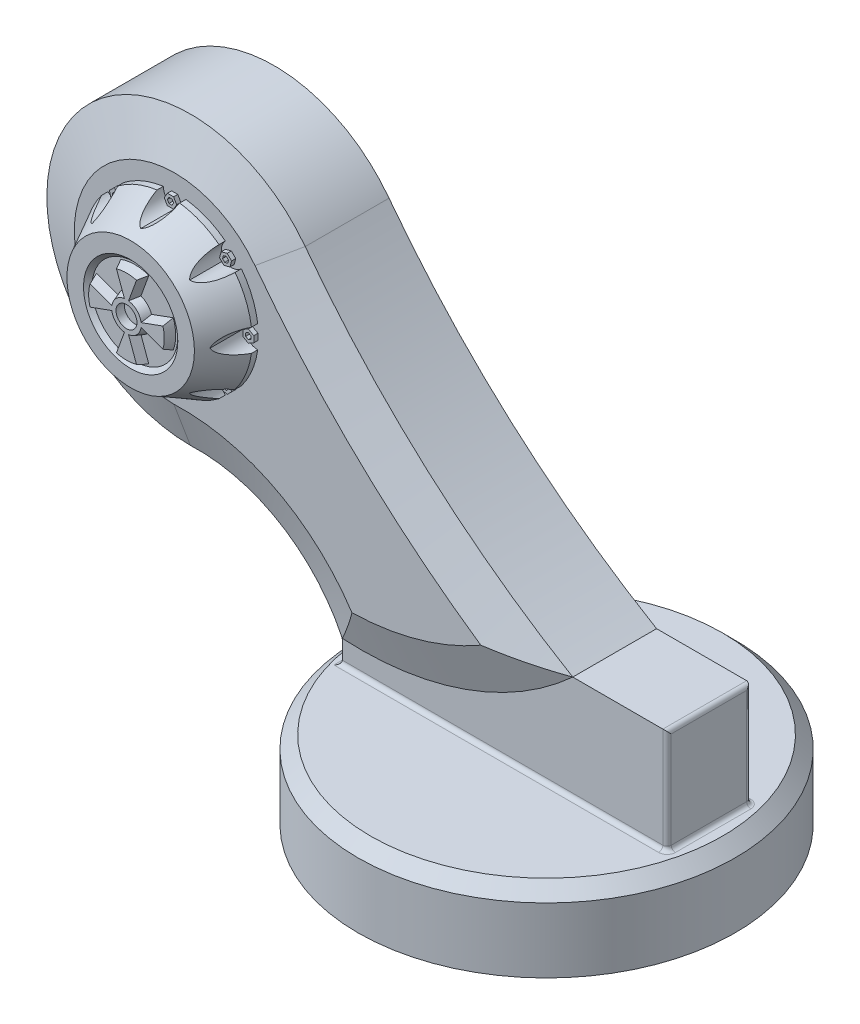
SolidWorks part; units mm, degrees
ref_plane "Front Plane" through (0, 0, 0) normal (0, 0, 1) x (1, 0, 0)
ref_plane "Top Plane" through (0, 0, 0) normal (0, 1, 0) x (1, 0, 0)
ref_plane "Right Plane" through (0, 0, 0) normal (1, 0, 0) x (0, 0, -1)
sketch "Sketch1" plane through (0, 0, 0) normal (0, 1, 0) x (1, 0, 0)
  circle A0 centre (0, 0) radius 90
  dimension "D1" = 180
extrude "Boss-Extrude1" add sketch "Sketch1" along normal blind 37
chamfer "Chamfer1" distance 6 angle 45 1 edges at (0, 37, 90)
sketch "Sketch2" plane through (0, 37, 0) normal (0, 1, 0) x (1, 0, 0)
  line L1 (-77.5, 20) -> (77.5, 20)
  line L2 (-77.5, 20) -> (-77.5, -20)
  line L3 (-77.5, -20) -> (77.5, -20)
  line L4 (77.5, 20) -> (77.5, -20)
  line L5 (-77.5, 20) -> (77.5, -20) construction
  line L6 (-77.5, -20) -> (77.5, 20) construction
  point P0 (0, 0)
  dimension "D1" = 155
  dimension "D2" = 40
extrude "Boss-Extrude2" add sketch "Sketch2" along normal blind 50
sketch "Sketch3" plane through (0, 0, 20) normal (0, 0, 1) x (1, 0, 0)
  line L0 (-77.5, 87) -> (32.5, 87)
  line L1 (-77.5, 87) -> (77.5, 87) construction
  line L2 (-77.5, 87) -> (-77.5, 48)
  line L3 (-77.5, 87) -> (-77.5, 37) construction
  arc A0 (32.5, 87) -> (-77.5, 48) centre (-68.6761, 197.7402) cw
  dimension "D3" = 150
  dimension "D1" = 39
  dimension "D2" = 110
extrude "Cut-Extrude1" cut sketch "Sketch3" against normal blind 50
sketch "Sketch4" plane through (0, 0, 0) normal (0, 0, 1) x (1, 0, 0)
  line L0 (-150, 0) -> (-150, 160)
  line L1 (-150, 0) -> (0, 0)
  circle A0 centre (-150, 160) radius 68.5
  arc A1 (-150, 91.5) -> (-77.5, 48) centre (-146.4719, 15.2134) cw
  arc A2 (32.5, 87) -> (-95.1949, 201.0933) centre (256.2098, 465.8851) cw
  arc A3 (-77.5, 48) -> (32.5, 87) centre (-68.6761, 197.7402) ccw construction
  arc A4 (-77.5, 48) -> (32.5, 87) centre (-68.6761, 197.7402) ccw
  dimension "D3" = 137
  dimension "D4" = 440
  dimension "D1" = 150
  dimension "D2" = 160
extrude "Boss-Extrude3" add sketch "Sketch4" along normal up to vertex (20 mm away) and the other way up to vertex (20 mm away)
sketch "Sketch5" plane through (0, 0, 20) normal (0, 0, 1) x (1, 0, 0)
  arc A0 (-77.5, 48) -> (32.5, 87) centre (-68.6761, 197.7402) ccw construction
  arc A1 (-77.5, 48) -> (32.5, 87) centre (-68.6761, 197.7402) ccw
  arc A2 (-95.1949, 201.0933) -> (32.5, 87) centre (256.2098, 465.8851) ccw construction
  arc A3 (-95.1949, 201.0933) -> (32.5, 87) centre (256.2098, 465.8851) ccw
  circle A4 centre (-150, 160) radius 68.5 construction
  circle A5 centre (-150, 160) radius 68.5
  arc A6 (-77.5, 48) -> (-150, 91.5) centre (-146.4719, 15.2134) ccw construction
  arc A7 (-77.5, 48) -> (-150, 91.5) centre (-146.4719, 15.2134) ccw
extrude "Boss-Extrude4" add sketch "Sketch5" along normal blind 7.5 draft 70
sketch "Sketch6" plane through (0, 0, 27.5) normal (0, 0, 1) x (1, 0, 0)
  circle A1 centre (-150, 160) radius 40
  dimension "D1" = 80
extrude "Boss-Extrude5" add sketch "Sketch6" along normal blind 3
sketch "Sketch7" plane through (0, 0, 30.5) normal (0, 0, 1) x (1, 0, 0)
  circle A0 centre (-150, 160) radius 40 construction
  circle A1 centre (-150, 160) radius 40
extrude "Boss-Extrude6" add sketch "Sketch7" along normal blind 18 draft 28
sketch "Sketch8" plane through (0, 0, 48.5) normal (0, 0, 1) x (1, 0, 0)
  line L0 (-150, 160) -> (-150, 239.5736) construction
  arc A0 (-155.4194, 199.6312) -> (-150, 193) centre (-148.422, 199.8198) ccw
  circle A1 centre (-150, 160) radius 40 construction
  arc A2 (-144.5806, 199.6312) -> (-150, 193) centre (-151.578, 199.8198) cw
  circle A3 centre (-150, 160) radius 40 construction
  arc A4 (-144.5806, 199.6312) -> (-155.4194, 199.6312) centre (-150, 160) ccw
  point P12 (-150, 200)
  dimension "D1" = 7
  dimension "D2" = 7
extrude "Cut-Extrude2" cut sketch "Sketch8" against normal up to surface (21 mm away)
sketch "Sketch9" plane through (0, 0, 27.5) normal (0, 0, 1) x (1, 0, 0)
  line L0 (-150, 160) -> (-150, 239.5736) construction
  line L1 (-147.0307, 197.1747) -> (-148.5154, 199.7462)
  line L2 (-148.5154, 199.7462) -> (-151.4846, 199.7462)
  line L3 (-151.4846, 199.7462) -> (-152.9693, 197.1747)
  line L4 (-152.9693, 197.1747) -> (-151.4846, 194.6033)
  line L5 (-151.4846, 194.6033) -> (-148.5154, 194.6033)
  line L6 (-148.5154, 194.6033) -> (-147.0307, 197.1747)
  line L14 (-148.5154, 197.1747) -> (-149.2577, 198.4605)
  line L15 (-149.2577, 198.4605) -> (-150.7423, 198.4605)
  line L16 (-150.7423, 198.4605) -> (-151.4846, 197.1747)
  line L17 (-151.4846, 197.1747) -> (-150.7423, 195.889)
  line L18 (-150.7423, 195.889) -> (-149.2577, 195.889)
  line L19 (-149.2577, 195.889) -> (-148.5154, 197.1747)
  circle A0 centre (-150, 197.1747) radius 2.5714 construction
  circle A1 centre (-150, 197.1747) radius 1.2857 construction
extrude "Boss-Extrude7" add sketch "Sketch9" along normal blind 2
pattern_circular "CirPattern1" count 8 over 360 about axis through (-150, 160, 0) along (0, 0, 1) of "Cut-Extrude2", "Boss-Extrude7"
sketch "Sketch10" plane through (0, 0, 48.5) normal (0, 0, 1) x (1, 0, 0)
  circle A0 centre (-150, 160) radius 22.5
  dimension "D1" = 45
extrude "Cut-Extrude3" cut sketch "Sketch10" against normal blind 2 draft 45
sketch "Sketch11" plane through (0, 0, 46.5) normal (0, 0, 1) x (1, 0, 0)
  line L0 (-156.6694, 178.324) -> (-152.9072, 167.9874)
  line L1 (-150, 168.5) -> (-150, 179.5) construction
  line L2 (-143.3306, 178.324) -> (-147.0928, 167.9874)
  line L3 (-131.676, 153.3306) -> (-142.0126, 157.0928)
  line L4 (-131.676, 166.6694) -> (-142.0126, 162.9072)
  line L5 (-156.6694, 141.676) -> (-152.9072, 152.0126)
  line L6 (-143.3306, 141.676) -> (-147.0928, 152.0126)
  line L7 (-168.324, 166.6694) -> (-157.9874, 162.9072)
  line L8 (-168.324, 153.3306) -> (-157.9874, 157.0928)
  circle A0 centre (-150, 160) radius 19.5
  arc A1 (-152.9072, 167.9874) -> (-157.9874, 162.9072) centre (-150, 160) ccw
  arc A2 (-142.0126, 162.9072) -> (-147.0928, 167.9874) centre (-150, 160) ccw
  arc A3 (-147.0928, 152.0126) -> (-142.0126, 157.0928) centre (-150, 160) ccw
  arc A4 (-157.9874, 157.0928) -> (-152.9072, 152.0126) centre (-150, 160) ccw
  point P25 (-150, 160)
  dimension "D1" = 39
  dimension "D2" = 17
  dimension "D3" = 20
  dimension "D4" = 4
extrude "Boss-Extrude8" add sketch "Sketch11" along normal blind 4 draft 20
sketch "Sketch12" plane through (0, 0, 50.5) normal (0, 0, 1) x (1, 0, 0)
  circle A0 centre (-150, 160) radius 5
  dimension "D1" = 10
extrude "Cut-Extrude4" cut sketch "Sketch12" against normal up to surface (4 mm away) up to face at (-129.5, 160, 46.5)
fillet "Fillet5" radius 2 8 edges at (0, 37, -20) (77.5, 37, 0) (-77.5, 48, 0) (-77.5, 37, 0) (77.5, 62, -20) (77.5, 87, 0) (77.5, 62, 20) (0, 37, 20)
sketch "Sketch13" plane through (0, 0, -20) normal (0, 0, -1) x (-1, 0, 0)
  circle A0 centre (150, 160) radius 15
  dimension "D1" = 30
extrude "Cut-Extrude5" cut sketch "Sketch13" against normal blind 20
sketch "Sketch14" plane through (0, 0, 0) normal (0, -1, 0) x (1, 0, 0)
  circle A0 centre (0, 0) radius 16.2005
extrude "Cut-Extrude6" cut sketch "Sketch14" against normal blind 15
